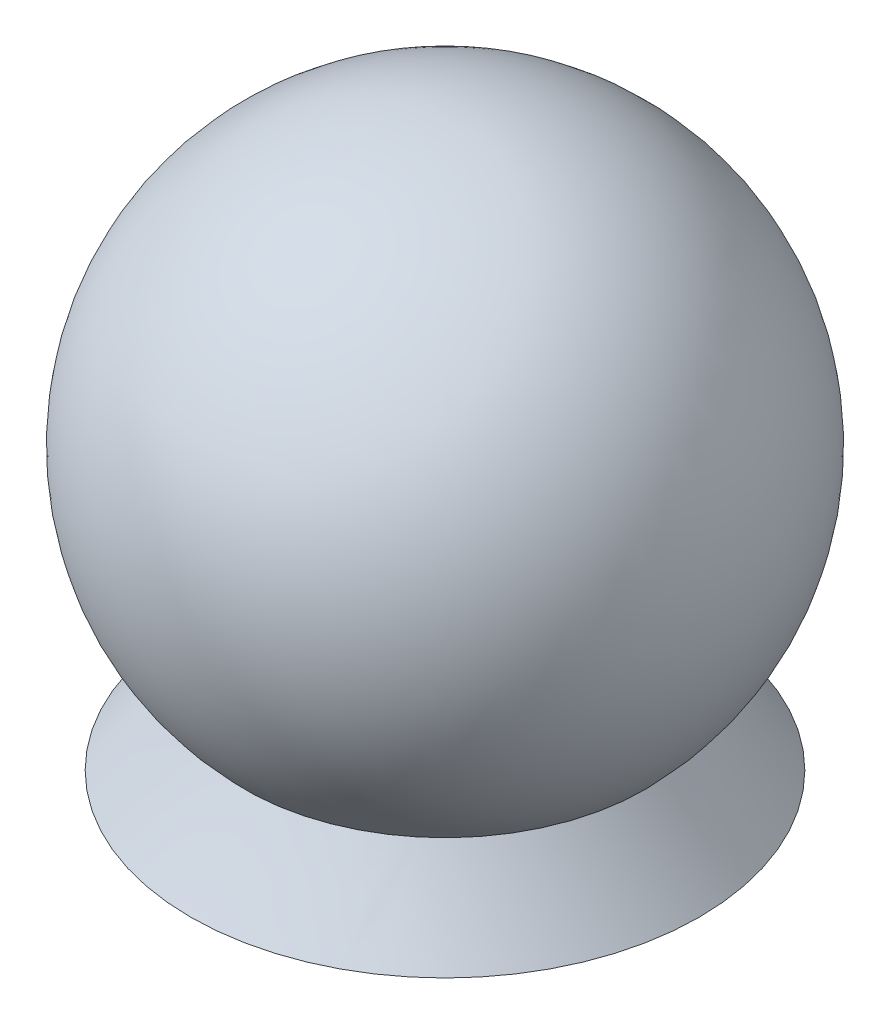
SolidWorks part; units mm, degrees
ref_plane "정면" through (0, 0, 0) normal (0, 0, 1) x (1, 0, 0)
ref_plane "윗면" through (0, 0, 0) normal (0, 1, 0) x (1, 0, 0)
ref_plane "우측면" through (0, 0, 0) normal (1, 0, 0) x (0, 0, -1)
sketch "스케치1" plane through (0, 0, 0) normal (0, 1, 0) x (1, 0, 0)
  circle A0 centre (0, 0) radius 2
sketch "스케치2" plane through (0, 0, 0) normal (0, 0, 1) x (1, 0, 0)
  line L0 (0, 0) -> (0, 4.4319)
  arc A0 (0, 4.4319) -> (0, 0) centre (0, 2.2159) ccw
ref_plane "평면1" through (0, 1, 0) normal (0, 1, 0) x (1, 0, 0)
sketch "스케치6" plane through (0, 1, 0) normal (0, 1, 0) x (1, 0, 0)
  circle A0 centre (0, 0) radius 1.3658
loft "로프트1" add profiles "스케치1", "스케치6" connector at (0.9425, 0, 1.764) connector at (1.0262, 1, 0.9013)
revolve "회전2" add sketch "스케치2" angle 360 about L0
